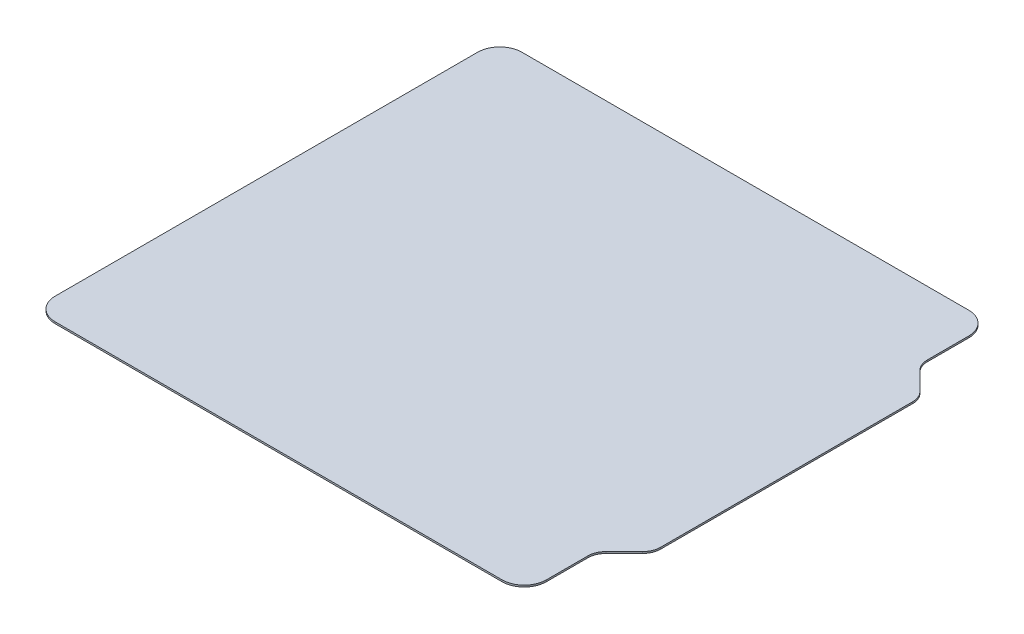
SolidWorks part; units mm, degrees
material "AISI 1020 Steel, Cold Rolled"
ref_plane "Front Plane" through (0, 0, 0) normal (0, 0, 1) x (1, 0, 0)
ref_plane "Top Plane" through (0, 0, 0) normal (0, 1, 0) x (1, 0, 0)
ref_plane "Right Plane" through (0, 0, 0) normal (1, 0, 0) x (0, 0, -1)
sketch "Sketch1" plane through (0, 0, 0) normal (0, 1, 0) x (1, 0, 0)
  line L1 (-117, 105) -> (117, 105)
  line L2 (-117, 105) -> (-117, -105)
  line L3 (-117, -105) -> (117, -105)
  line L4 (117, 105) -> (117, -105)
  line L5 (-117, 105) -> (117, -105) construction
  line L6 (-117, -105) -> (117, 105) construction
  point P0 (0, 0)
  dimension "D1" = 234
  dimension "D2" = 210
extrude "Boss-Extrude1" add sketch "Sketch1" along normal blind 0.76
sketch "Sketch2" plane through (0, 0.76, 0) normal (0, 1, 0) x (1, 0, 0)
  line L0 (117, 60) -> (104, 73)
  line L1 (117, -105) -> (117, 105) construction
  line L2 (104, 73) -> (104, 105)
  line L3 (117, 105) -> (-117, 105) construction
  line L4 (104, 105) -> (117, 105)
  line L5 (117, 105) -> (117, 60)
  line L6 (-0.418, 0) -> (0.418, 0) construction
  line L7 (104, -105) -> (117, -105)
  line L8 (104, -73) -> (104, -105)
  line L9 (117, -60) -> (104, -73)
  line L10 (117, -105) -> (117, -60)
  dimension "D1" = 45
  dimension "D2" = 32
  dimension "D3" = 13
extrude "Cut-Extrude1" cut sketch "Sketch2" against normal blind 0.76
fillet "Fillet1" radius 8 4 edges at (104, 0.38, 73) (117, 0.38, 60) (117, 0.38, -60) (104, 0.38, -73)
fillet "Fillet2" radius 10 4 edges at (-117, 0.38, -105) (-117, 0.38, 105) (104, 0.38, 105) (104, 0.38, -105)
